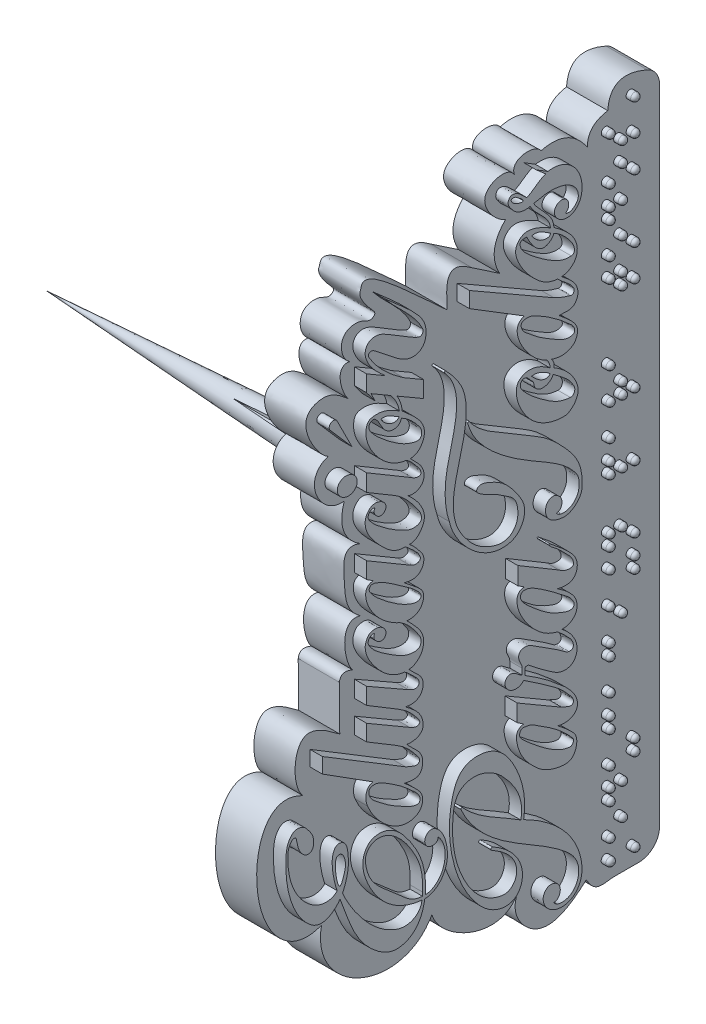
SolidWorks part; units mm, degrees
ref_plane "Alzado" through (0, 0, 0) normal (1, 0, 0) x (0, 1, 0)
ref_plane "Planta" through (0, 0, 0) normal (0, 0, 1) x (0, 1, 0)
ref_plane "Vista lateral" through (0, 0, 0) normal (0, 1, 0) x (-1, 0, 0)
sketch "Croquis1" plane through (0, 0, 0) normal (1, 0, 0) x (0, 1, 0)
  line L0 (-102.9215, 14.1156) -> (89.1062, 14.1156) construction
  line L1 (-85, 70) -> (85, 70) construction
  line L2 (-85, 70) -> (-85, -70) construction
  line L3 (-85, -70) -> (85, -70) construction
  line L4 (85, 70) -> (85, -70) construction
  line L5 (-85, 70) -> (85, -70) construction
  line L6 (-85, -70) -> (85, 70) construction
  line L7 (-124.4201, -60.3496) -> (113.099, -60.3496) construction
  line L8 (-82.6448, -39.616) -> (-82.6448, -50.4608)
  line L9 (-82.6448, -50.4608) -> (81.3909, -50.4608)
  spline S0 degree 3 poles (-57.3183, 31.5751) (-59.6603, 37.38) (-50.6709, 49.5862) (-25.7042, 47.5365) (-26.6427, 38.3656) (-27.8824, 36.0647) knots 0 0 0 0 0.354827 0.843229 0.974584 0.974584 0.974584 0.974584
  spline S1 degree 3 poles (-27.8824, 36.0647) (-26.8745, 37.0409) (-21.9922, 38.7753) (-11.8785, 36.5221) (-18.2243, 28.7209) (-19.3798, 27.1503) knots 0.077094 0.077094 0.077094 0.077094 0.266164 0.614207 1 1 1 1
  spline S2 degree 1 poles (-19.3798, 27.1503) (-8.4844, 27.2308) knots 0 0 1 1
  spline S3 degree 2 poles (-8.4844, 27.2308) (-6.1864, 26.9833) (-7.4593, 24.0317) knots 0 0 0 1 1 1
  spline S4 degree 3 poles (-7.4593, 24.0317) (-5.479, 25.9604) (4.6696, 27.8327) (2.9757, 22.117) knots 0 0 0 0 1 1 1 1
  spline S5 degree 3 poles (2.9757, 22.117) (5.5942, 25.8408) (10.9508, 25.8036) (19.9981, 26.6673) (18.1231, 22.117) knots 0 0 0 0 0.550537 1 1 1 1
  spline S6 degree 2 poles (18.1231, 22.117) (21.9702, 28.2845) (29.0551, 26.0729) knots 0 0 0 1 1 1
  spline S7 degree 3 poles (29.0551, 26.0729) (28.1951, 31.7606) (38.0923, 36.9327) (40.4039, 29.9176) knots 0 0 0 0 1 1 1 1
  spline S8 degree 3 poles (40.4039, 29.9176) (40.8758, 31.7815) (51.1967, 39.0102) (54.1428, 29.6378) (51.4152, 26.7401) (50.0352, 25.0248) knots 0 0 0 0 0.547016 0.715017 1 1 1 1
  spline S9 degree 3 poles (50.0352, 25.0248) (51.2452, 26.4664) (58.6684, 28.9911) (57.6422, 24.5742) knots 0 0 0 0 1 1 1 1
  spline S10 degree 3 poles (57.6422, 24.5742) (58.5649, 26.5416) (64.4147, 28.0831) (65.4745, 22.2237) (63.4708, 19.7827) (64.7939, 18.3202) (66.36, 19.8599) (69.5572, 22.3126) (71.0006, 22.3852) (71.715, 21.8879) (76.7031, 21.8392) (57.3827, 1.9867) (56.8213, 1.1788) knots 0 0 0 0 0.22866 0.372767 0.46177 0.486324 0.534034 0.642403 0.758615 0.782831 0.884561 1 1 1 1
  spline S11 degree 3 poles (-57.3183, 31.5751) (-71.6053, 34.513) (-81.578, 12.1878) (-68.5411, 4.7917) knots 0 0 0 0 1 1 1 1
  spline S12 degree 3 poles (-68.5411, 4.7917) (-75.1077, 2.9582) (-82.4626, -11.6999) (-74.4154, -15.9897) knots 0 0 0 0 1 1 1 1
  spline S13 degree 3 poles (-74.4154, -15.9897) (-78.3688, -14.0059) (-87.8936, -20.9461) (-83.6056, -28.6593) (-79.9178, -32.6901) knots 0 0 0 0 0.492525 1 1 1 1
  spline S14 degree 3 poles (-79.9178, -32.6901) (-84.1528, -34.8815) (-82.6448, -36.9407) (-82.6448, -39.616) knots 0 0 0 0 1 1 1 1
  spline S15 degree 3 poles (56.8213, 1.1788) (59.4241, 0.8853) (68.4666, 2.8376) (62.5364, -4.9778) knots 0 0 0 0 1 1 1 1
  spline S16 degree 1 poles (62.5364, -4.9778) (58.0243, -11.665) knots 0 0 1 1
  spline S17 degree 2 poles (58.0243, -11.665) (63.9267, -8.3863) (68.6781, -13.114) knots 0 0 0 1 1 1
  spline S18 degree 3 poles (68.6781, -13.114) (69.3817, -10.7651) (75.4734, -5.4705) (79.0736, -11.5853) (78.2326, -14.5514) (76.8919, -15.2804) knots 0 0 0 0 0.53381 0.759379 0.979689 0.979689 0.979689 0.979689
  spline S19 degree 3 poles (76.8919, -15.2804) (77.831, -14.9048) (80.7449, -15.427) (80.5824, -20.5896) (78.7651, -21.726) knots 0.033423 0.033423 0.033423 0.033423 0.278907 1 1 1 1
  spline S20 degree 2 poles (78.7651, -21.726) (80.5238, -28.3502) (73.9377, -32.9389) knots 0 0 0 1 1 1
  spline S21 degree 2 poles (73.9377, -32.9389) (78.3158, -32.9335) (79.1127, -37.8873) knots 0 0 0 1 1 1
  spline S22 degree 2 poles (79.1127, -37.8873) (88.058, -38.6156) (81.3909, -50.4608) knots 0 0 0 1 1 1
  point P0 (0, 0)
  dimension "D1" = 170
  dimension "D2" = 140
extrude "Saliente-Extruir2" add sketch "Croquis1" along normal blind 10
sketch "Croquis2" plane through (0, 0, 0) normal (-1, 0, 0) x (0, -1, 0)
  line L0 (0.6269, -50.4608) -> (0.6269, 25.9378) construction
  line L1 (82.6448, -50.4608) -> (-81.3909, -50.4608) construction
  line L2 (82.6448, -1.5809) -> (-84.2357, -1.5809) construction
  line L3 (82.6448, -50.4608) -> (-84.2357, -50.4608) construction
  line L4 (82.6448, -50.4608) -> (82.6448, 47.299) construction
  line L5 (82.6448, 47.299) -> (-84.2357, 47.299) construction
  line L6 (-84.2357, -50.4608) -> (-84.2357, 47.299) construction
  line L7 (82.6448, -11.5809) -> (-84.2357, -11.5809) construction
  parabola Q0 (-81.3909, -50.4608) -> (-79.1127, -37.8873) focus (-82.0968, -40.8467) apex (-83.5176, -39.835) construction
  parabola Q1 (-81.3909, -50.4608) -> (-79.1127, -37.8873) focus (-82.0968, -40.8467) apex (-83.5176, -39.835) construction
  spline S0 degree 3 poles (-2.9757, 22.117) (-4.6696, 27.8327) (5.479, 25.9604) (7.4593, 24.0317) knots 0 0 0 0 1 1 1 1 construction
  spline S1 degree 3 poles (27.8824, 36.0647) (26.6427, 38.3656) (25.7042, 47.5365) (50.6709, 49.5862) (59.6603, 37.38) (57.3183, 31.5751) knots 0 0 0 0 0.131354 0.619757 0.974584 0.974584 0.974584 0.974584 construction
  point P11 (40.0069, 47.299)
  point P17 (-84.2357, -42.2008)
  dimension "D1" = 8.26
  dimension "D2" = 39.38
  dimension "D3" = 10
ref_plane "Plano1" through (0, -0.6269, 0) normal (0, 1, 0) x (0, 0, 1)
sketch "Croquis3" plane through (0, -0.6269, 0) normal (0, 1, 0) x (0, 0, 1)
  line L0 (-11.665, 0) -> (-11.665, -100)
  line L1 (-11.665, -100) -> (-5.665, 0)
  line L2 (-50.4608, 0) -> (47.299, 0) construction
  line L3 (-5.665, 0) -> (-11.665, 0)
  dimension "D1" = 6
  dimension "D2" = 100
revolve "Revolución1" add sketch "Croquis3" angle 360 about L0
sketch "Croquis4" plane through (0, 0, 0) normal (-1, 0, 0) x (0, -1, 0)
  line L0 (0.6269, -17.665) -> (0.6269, -5.665) construction
  line L1 (-5.3731, -11.665) -> (6.6269, -11.665) construction
  line L2 (2.6269, -17.3219) -> (2.6269, -13.665)
  line L4 (2.6269, -6.0081) -> (2.6269, -9.665)
  line L5 (2.6269, -9.665) -> (6.2838, -9.665)
  line L7 (2.6269, -13.665) -> (6.2838, -13.665)
  line L8 (-1.3731, -17.3219) -> (-1.3731, -13.665)
  line L9 (-1.3731, -13.665) -> (-5.0299, -13.665)
  line L10 (-1.3731, -6.0081) -> (-1.3731, -9.665)
  line L11 (-1.3731, -9.665) -> (-5.0299, -9.665)
  circle A0 centre (0.6269, -11.665) radius 6 construction
  arc A1 (6.2838, -9.665) -> (2.6269, -6.0081) centre (0.6269, -11.665) ccw
  arc A2 (6.2838, -13.665) -> (2.6269, -17.3219) centre (0.6269, -11.665) cw
  arc A3 (-5.0299, -13.665) -> (-1.3731, -17.3219) centre (0.6269, -11.665) ccw
  arc A4 (-5.0299, -9.665) -> (-1.3731, -6.0081) centre (0.6269, -11.665) cw
  point P6 (0.6269, -11.665)
  point P8 (0.6269, -11.665)
  dimension "D1" = 4
  dimension "D2" = 4
extrude "Cortar-Extruir1" cut sketch "Croquis4" along normal through all
sketch "Croquis5" plane through (10, 0, 0) normal (1, 0, 0) x (0, 1, 0)
  line L0 (-30.4977, 22.0411) -> (-22.6878, 34.3782)
  line L1 (-22.6878, 34.3782) -> (-18.9988, 34.3782)
  line L2 (-18.9988, 34.3782) -> (-31.2431, 14.2065)
  line L3 (-25.6704, 16.365) -> (-21.3142, 23.6252)
  line L4 (-21.3142, 23.6252) -> (-17.3898, 23.6252)
  line L5 (-17.3898, 23.6252) -> (-23.4923, 13.1469)
  line L6 (-18.26, 15.9553) -> (-13.6411, 23.6252)
  line L7 (-13.6411, 23.6252) -> (-9.6181, 23.6252)
  line L8 (-9.6181, 23.6252) -> (-15.3979, 13.483)
  line L9 (11.7696, 22.0411) -> (12.8183, 23.6252)
  line L10 (12.8183, 23.6252) -> (16.7733, 23.6252)
  line L11 (16.7733, 23.6252) -> (10.6011, 13.1469)
  line L12 (27.0179, 16.7117) -> (31.1151, 23.6252)
  line L13 (31.1151, 23.6252) -> (35.2573, 23.6252)
  line L14 (35.2573, 23.6252) -> (28.6961, 12.5539)
  line L15 (49.3274, 21.5592) -> (52.0818, 23.6252)
  line L16 (52.0818, 23.6252) -> (56.0401, 23.6252)
  line L17 (56.0401, 23.6252) -> (53.3778, 19.0421)
  line L18 (49.3274, 21.5592) -> (51.3704, 22.5922)
  line L19 (51.3704, 22.5922) -> (48.5969, 17.8177)
  line L20 (47.708, 16.2875) -> (43.9264, 9.7775)
  line L21 (43.9264, 9.7775) -> (47.9268, 9.7775)
  line L22 (47.9268, 9.7775) -> (50.7842, 14.6965)
  line L23 (-36.5891, -14.4731) -> (-35.5305, -12.9048)
  line L24 (-35.5305, -12.9048) -> (-31.3942, -12.9048)
  line L25 (-31.3942, -12.9048) -> (-37.6673, -23.6868)
  line L26 (-7.8732, -14.6713) -> (-6.8254, -13.0472)
  line L27 (-6.8254, -13.0472) -> (-2.5643, -13.0472)
  line L28 (-2.5643, -13.0472) -> (-8.5231, -23.0594)
  line L29 (49.0645, -14.6713) -> (57.2905, -1.3112)
  line L30 (57.2905, -1.3112) -> (61.1001, -1.3112)
  line L31 (61.1001, -1.3112) -> (49.3274, -21.8088)
  line L32 (-60.5363, 10.0615) -> (-59.6392, 10.0615)
  line L33 (42.5241, 27.1794) -> (48.6046, 32.4718)
  line L34 (42.5241, 27.1794) -> (49.7281, 30.7967)
  line L35 (-26.5452, -14.7609) -> (-25.0608, -14.7609)
  line L36 (-26.1554, -14.1147) -> (-24.6961, -14.1147)
  line L37 (76.3432, -19.832) -> (78.3569, -17.5177)
  line L38 (78.3569, -17.5177) -> (76.6086, -20.3374)
  arc A0 (48.6046, 32.4718) -> (49.7281, 30.7967) centre (49.272, 31.7051) cw
  arc A1 (46.7383, 4.7071) -> (47.0407, 4.379) centre (46.8895, 4.5431) cw
  ellipse E0 centre (34.8468, 28.3326) end of major axis (36.1076, 30.4854) minor radius 2.1626
  spline S0 degree 3 poles (-32.8753, 40.7809) (-34.3802, 40.4669) (-37.0315, 40.1552) (-37.9946, 37.6514) (-37.3498, 36.6243) (-36.0991, 36.4283) (-34.4623, 36.5674) (-32.8648, 37.7082) (-31.5106, 38.7912) (-31.1895, 40.0213) (-31.1194, 41.2018) (-32.1231, 42.2284) (-33.817, 43.0691) (-35.9852, 43.257) (-42.6275, 43.2661) (-49.4687, 41.3481) (-53.3655, 36.734) (-54.6854, 33.7936) (-52.5646, 31.007) (-51.081, 30.0928) knots 0 0 0 0 0.108114 0.133301 0.15011 0.176379 0.206942 0.251601 0.297171 0.308781 0.330505 0.367881 0.388722 0.449419 0.4998 0.809316 0.834126 0.878153 1 1 1 1
  spline S1 degree 3 poles (-48.9999, 30.777) (-50.0879, 31.7419) (-50.4065, 34.7517) (-48.0166, 38.3827) (-44.5897, 40.971) (-40.6201, 42.4403) (-36.9284, 42.8214) (-33.9844, 42.7371) (-32.5521, 41.5219) (-32.8753, 40.7809) knots 0 0 0 0 0.159033 0.321236 0.4893 0.658852 0.811177 0.925085 1 1 1 1
  spline S2 degree 3 poles (-48.9999, 30.777) (-47.1529, 31.4095) (-44.3644, 32.0377) (-41.1112, 32.0057) (-39.4998, 31.2812) (-39.2053, 30.0434) (-39.8032, 28.827) (-41.2423, 28.2718) (-43.0409, 28.1097) (-44.7609, 27.9724) (-47.3, 28.3578) (-48.9998, 28.8703) (-50.1929, 29.4683) knots 0 0 0 0 0.260758 0.368098 0.436423 0.467936 0.526484 0.597505 0.66092 0.767128 0.823696 1 1 1 1
  spline S3 degree 3 poles (-46.1216, 28.9658) (-49.4615, 30.1919) (-46.2018, 31.0145) (-44.5749, 31.1947) (-43.0781, 31.2524) (-41.8296, 31.0322) (-41.5877, 30.1974) (-41.9671, 29.4227) (-42.8967, 29.028) (-44.5301, 28.6081) (-46.1216, 28.9658) (-49.4615, 30.1919) (-46.2018, 31.0145) knots -0.383453 -0.313119 -0.129387 0 0.154158 0.272418 0.382012 0.456693 0.492971 0.539173 0.616547 0.686881 0.870613 1 1.154158 1.272418 1.382012 only from (-48.3835, 30.0928) to (-48.3835, 30.0928)
  spline S4 degree 3 poles (-51.081, 30.0928) (-54.3854, 28.7515) (-60.3811, 27.0599) (-66.2373, 22.0009) (-69.1599, 16.8685) (-67.2807, 11.1802) (-63.3803, 9.8373) (-61.3313, 9.5286) knots 0 0 0 0 0.318574 0.533737 0.673711 0.810653 1 1 1 1
  spline S5 degree 3 poles (-50.1929, 29.4683) (-52.7679, 28.3332) (-57.9916, 25.0937) (-63.2745, 19.7033) (-65.3126, 13.4525) (-63.4453, 10.3811) (-61.253, 10.221) knots 0 0 0 0 0.305324 0.676273 0.795053 1 1 1 1
  spline S6 degree 3 poles (-61.253, 10.221) (-61.0094, 12.9445) (-59.1446, 17.8712) (-54.1089, 22.0097) (-49.5346, 24.1939) (-45.6585, 24.963) (-42.2603, 23.05) (-41.833, 19.6005) (-43.3284, 16.5185) (-45.8717, 14.1634) (-48.6344, 12.3059) (-53.2209, 9.7295) (-57.471, 9.1432) (-60.5363, 9.3474) knots 0 0 0 0 0.157619 0.290223 0.363353 0.451183 0.506001 0.566054 0.62999 0.698057 0.763117 0.821877 1 1 1 1
  spline S7 degree 3 poles (-60.5363, 10.0615) (-60.4315, 10.7862) (-60.1786, 12.5343) (-57.9714, 15.1639) (-55.0045, 18.4788) (-51.8323, 22.3612) (-47.8915, 23.8396) (-44.7064, 24.0894) (-42.809, 21.9292) (-43.024, 19.0148) (-45.4064, 15.3815) (-49.5738, 12.4184) (-54.7209, 10.0546) (-58.0346, 10.0592) (-59.6392, 10.0615) knots 0 0 0 0 0.045785 0.110435 0.210486 0.334029 0.417166 0.475731 0.520954 0.580199 0.646906 0.791941 0.899251 1 1 1 1
  spline S8 degree 3 poles (-49.9407, 6.2825) (-50.7221, 6.2114) (-51.3167, 7.3771) (-50.7667, 9.067) (-49.2157, 9.7669) (-47.8688, 9.1169) (-47.4082, 7.9224) (-47.8668, 6.803) (-48.9098, 5.6745) (-50.6697, 4.6821) (-53.2743, 4.0227) (-56.0005, 3.9217) (-58.2431, 4.789) (-60.3787, 6.3007) (-61.3542, 8.1142) (-61.3313, 9.5286) knots 0 0 0 0 0.071311 0.131011 0.190199 0.247337 0.285436 0.329154 0.380499 0.464884 0.561183 0.694994 0.776359 0.838641 1 1 1 1
  spline S9 degree 3 poles (-60.5363, 9.3474) (-60.564, 8.4483) (-59.8552, 6.8761) (-56.3738, 3.9845) (-51.9735, 4.3417) (-49.9407, 6.2825) knots 0 0 0 0 0.198499 0.371277 1 1 1 1
  spline S10 degree 2 poles (-41.6654, 18.06) (-38.9768, 21.6923) (-34.8857, 23.4339) knots 0 0 0 1 1 1
  spline S11 degree 3 poles (-34.8857, 23.4339) (-34.0906, 23.7515) (-32.3111, 24.0568) (-30.572, 23.1832) (-30.4977, 22.0411) knots 0 0 0 0 0.485788 1 1 1 1
  spline S12 degree 3 poles (-41.6654, 18.06) (-42.3986, 16.9398) (-43.3898, 15.0022) (-43.2455, 12.1543) (-41.8787, 10.0564) (-39.1625, 9.8582) (-36.8543, 11.8502) (-35.5255, 13.3917) (-34.6128, 14.4067) knots 0 0 0 0 0.236614 0.362101 0.48322 0.639456 0.763526 1 1 1 1
  spline S13 degree 3 poles (-40.6946, 10.9609) (-40.3903, 12.8252) (-39.1448, 14.9393) (-37.6665, 17.8519) (-35.4327, 20.6084) (-33.7314, 23.1321) (-31.7518, 23.1007) (-31.2827, 22.5692) (-31.0851, 21.3705) (-31.8864, 19.5488) (-33.392, 17.2339) (-35.0824, 14.7482) (-37.0941, 12.6053) (-38.4647, 10.9995) (-39.8145, 10.5247) (-40.6946, 10.9609) (-40.3903, 12.8252) (-39.1448, 14.9393) knots -0.083981 -0.054525 -0.041628 0 0.085966 0.20646 0.292539 0.428731 0.44798 0.464095 0.49008 0.557009 0.641477 0.750478 0.835345 0.916019 0.945475 0.958372 1 1.085966 1.20646 1.292539 only from (-40.4476, 12.1724) to (-40.4476, 12.1724)
  spline S14 degree 3 poles (-31.2431, 14.2065) (-31.4954, 13.791) (-31.7805, 12.8244) (-32.3805, 11.7184) (-31.94, 10.716) (-31.0117, 10.8255) (-30.1202, 11.5734) (-28.0239, 13.1991) (-26.5761, 14.8553) (-25.6704, 16.365) knots 0 0 0 0 0.125392 0.242085 0.298963 0.348525 0.442223 0.588193 1 1 1 1
  spline S15 degree 3 poles (-34.6128, 14.4067) (-34.7496, 13.4983) (-35.4629, 10.853) (-32.8319, 9.9131) (-29.6395, 10.1767) (-28.0685, 12.8244) (-26.67, 13.9022) knots 0 0 0 0 0.278768 0.418048 0.563003 1 1 1 1
  spline S16 degree 3 poles (-26.67, 13.9022) (-26.9516, 12.9077) (-26.6145, 9.794) (-21.7377, 9.9597) (-19.9279, 12.5545) (-18.6511, 14.2065) knots 0 0 0 0 0.313936 0.487109 1 1 1 1
  spline S17 degree 3 poles (-23.4923, 13.1469) (-23.7092, 12.5749) (-24.4199, 11.749) (-23.7114, 10.5495) (-22.7044, 11.0703) (-20.8333, 12.6799) (-19.6018, 13.7273) (-18.26, 15.9553) knots 0 0 0 0 0.194853 0.255549 0.328019 0.466069 1 1 1 1
  spline S18 degree 3 poles (-18.6511, 14.2065) (-18.8985, 13.209) (-18.944, 11.198) (-16.9063, 9.8461) (-13.827, 9.881) (-12.4616, 12.4027) (-11.1951, 13.3111) knots 0 0 0 0 0.281686 0.412944 0.576334 1 1 1 1
  spline S19 degree 3 poles (-15.3979, 13.483) (-15.6328, 12.976) (-16.4144, 11.8498) (-15.4388, 10.7448) (-14.194, 11.1159) (-12.9561, 12.5512) (-11.7383, 13.604) (-11.1951, 14.496) knots 0 0 0 0 0.252349 0.329617 0.447788 0.639049 1 1 1 1
  spline S20 degree 3 poles (-11.1951, 13.3111) (-11.1786, 12.6141) (-10.61, 11.4044) (-9.2667, 10.2) (-7.7421, 9.764) (-4.407, 9.7889) (-2.2388, 12.4696) (-0.6949, 13.9022) knots 0 0 0 0 0.148996 0.285512 0.38061 0.491113 1 1 1 1
  spline S21 degree 3 poles (-11.1951, 14.496) (-11.1257, 15.8129) (-9.8111, 18.7994) (-6.291, 21.994) (-2.9718, 23.9384) (-0.7617, 23.9955) (0.1528, 23.6663) (1.0645, 23.1384) (1.4373, 22.0629) (1.4623, 20.8899) (0.8662, 19.7313) (0.0333, 19.0277) (-0.8625, 18.8995) (-1.7284, 19.195) (-1.9636, 20.256) (-1.2566, 21.5002) (-0.2394, 22.2156) (0.5693, 21.6497) knots 0 0 0 0 0.142885 0.345562 0.51692 0.54408 0.584366 0.622837 0.653405 0.704139 0.747462 0.792556 0.816848 0.844533 0.884115 0.91523 1 1 1 1
  spline S22 degree 3 poles (0.5693, 21.6497) (0.7039, 22.1733) (0.3651, 23.0472) (-0.8733, 23.4017) (-1.8324, 22.7341) (-3.1649, 21.6574) (-4.5178, 19.8541) (-6.1477, 17.3884) (-7.6569, 14.9172) (-8.2509, 12.6201) (-8.0802, 10.6437) (-6.2269, 10.2196) (-3.5165, 12.0259) (-1.4681, 13.63) (-0.3081, 15.5121) knots 0 0 0 0 0.059858 0.084589 0.133112 0.178045 0.278694 0.378635 0.509425 0.593264 0.648482 0.700592 0.76797 1 1 1 1
  spline S23 degree 3 poles (-0.3081, 15.5121) (0.4824, 17.2717) (2.304, 20.0154) (5.6832, 22.6917) (8.9806, 24.0787) (11.5742, 23.9247) (11.7696, 22.0411) knots 0 0 0 0 0.349521 0.588759 0.767778 1 1 1 1
  spline S24 degree 3 poles (-0.6949, 13.9022) (-0.9343, 12.7942) (-0.4522, 10.7658) (1.6189, 9.7936) (2.8478, 9.75) (3.8626, 10.1492) (5.493, 11.6662) (6.5376, 13.3498) (7.5617, 14.496) knots 0 0 0 0 0.267509 0.402149 0.498611 0.541617 0.649789 1 1 1 1
  spline S25 degree 3 poles (7.6462, 15.9241) (10.1866, 19.0064) (11.1853, 21.9828) (11.0882, 22.7824) (10.2945, 23.1392) (9.5666, 22.7365) (8.208, 21.7006) (6.1295, 19.2883) (3.7662, 16.0444) (2.2798, 13.072) (1.9119, 11.1988) (2.4385, 10.3789) (3.296, 10.4425) (3.9842, 11.0502) (4.5955, 11.7225) (5.5919, 12.7416) (7.6462, 15.9241) (10.1866, 19.0064) (11.1853, 21.9828) knots -0.355516 -0.339725 -0.248943 0 0.025214 0.046912 0.068041 0.09466 0.119729 0.23059 0.389513 0.497031 0.541805 0.563228 0.573881 0.617524 0.644484 0.660275 0.751057 1 1.025214 1.046912 1.068041 only from (10.9335, 21.2609) to (10.9335, 21.2609)
  spline S26 degree 3 poles (10.6011, 13.1469) (10.4033, 12.8112) (9.8549, 11.8359) (10.4667, 10.2937) (11.9078, 10.9475) (13.2454, 12.1923) (14.3707, 13.3792) (15.0135, 14.2065) knots 0 0 0 0 0.18999 0.314253 0.460996 0.61937 1 1 1 1
  spline S27 degree 3 poles (7.5617, 14.496) (7.2677, 13.4828) (6.9121, 11.0987) (9.183, 9.7347) (11.0782, 9.6872) (12.9527, 11.231) (14.3116, 12.3091) (15.0135, 13.3111) knots 0 0 0 0 0.288267 0.445397 0.571944 0.717436 1 1 1 1
  spline S28 degree 3 poles (15.0135, 14.2065) (14.8615, 16.7526) (17.5133, 19.6933) (21.0407, 22.7822) (23.9338, 24.1476) (26.4814, 23.8973) (27.9531, 22.308) (27.723, 20.3882) (26.7443, 18.9146) (24.8751, 18.8823) (24.3226, 20.3976) (25.2344, 21.6158) (26.2623, 22.0942) (26.8814, 21.5592) knots 0 0 0 0 0.257469 0.404494 0.516094 0.593904 0.669355 0.720454 0.795978 0.839171 0.895119 0.925934 1 1 1 1
  spline S29 degree 3 poles (26.8814, 21.5592) (27.0954, 22.0247) (26.9036, 22.9292) (25.5957, 23.4629) (24.3413, 22.5871) (23.1722, 21.4419) (21.0572, 18.7443) (18.9909, 15.6579) (17.652, 12.21) (18.505, 10.1974) (20.0998, 10.3899) (21.243, 11.1001) (23.8006, 13.0162) (25.9385, 14.8902) (27.0179, 16.7117) knots 0 0 0 0 0.049092 0.083265 0.127241 0.194236 0.257104 0.479655 0.581589 0.628504 0.6687 0.72549 0.770635 1 1 1 1
  spline S30 degree 3 poles (15.0135, 13.3111) (14.9143, 11.9258) (16.3437, 10.3322) (18.913, 9.3832) (22.2509, 10.3688) (24.2046, 12.2466) (25.5195, 13.7107) knots 0 0 0 0 0.276983 0.422942 0.572023 1 1 1 1
  spline S31 degree 3 poles (25.5195, 13.7107) (24.8284, 12.5371) (25.5252, 9.7865) (29.9097, 9.4817) (31.6722, 11.8848) (32.9555, 13.0649) knots 0 0 0 0 0.341874 0.528238 1 1 1 1
  spline S32 degree 3 poles (28.6961, 12.5539) (28.421, 12.3856) (27.6888, 10.3026) (29.5345, 10.5614) (30.9642, 11.8817) (32.4321, 12.9727) (33.0696, 14.0259) knots 0 0 0 0 0.260801 0.352343 0.552857 1 1 1 1
  spline S33 degree 3 poles (33.0696, 14.0259) (33.4098, 16.9926) (36.39, 20.8729) (41.2096, 23.598) (44.1316, 23.9082) (46.0104, 23.4117) (46.7526, 19.96) (45.5118, 17.6923) (44.3075, 15.6952) knots 0 0 0 0 0.340662 0.54387 0.625452 0.689244 0.744404 1 1 1 1
  spline S34 degree 3 poles (32.9555, 13.0649) (32.854, 10.9485) (38.4119, 7.3412) (42.3173, 13.4151) (43.9264, 15.0017) knots 0 0 0 0 0.387765 1 1 1 1
  spline S35 degree 3 poles (43.0647, 15.6952) (43.7052, 17.0431) (45.1478, 18.4945) (44.8019, 20.1684) knots 0 0 0 0 1 1 1 1
  spline S36 degree 3 poles (44.8019, 20.1684) (44.0548, 19.8014) (42.7981, 18.519) (42.1784, 16.5118) (43.0647, 15.6952) knots 0 0 0 0 0.44386 1 1 1 1
  spline S37 degree 3 poles (42.5241, 15.1835) (41.1069, 15.4879) (40.6761, 17.8412) (42.904, 20.1193) (44.7136, 20.6463) (45.5384, 21.6497) knots 0 0 0 0 0.390264 0.598106 1 1 1 1
  spline S38 degree 3 poles (45.5384, 21.6497) (45.6879, 22.0521) (45.5094, 22.8336) (44.2166, 23.2814) (42.868, 22.3291) (40.5799, 20.1613) (38.0542, 16.8143) (36.2183, 13.6653) (35.4577, 10.2113) (37.7346, 10.2131) (39.964, 11.8499) (41.6353, 13.5109) (42.5241, 15.1835) knots 0 0 0 0 0.048159 0.074575 0.142627 0.215099 0.445179 0.592365 0.67817 0.744905 0.783216 1 1 1 1
  spline S39 degree 2 poles (44.3075, 15.6952) (46.7398, 16.1406) (48.5969, 17.8177) knots 0 0 0 1 1 1
  spline S40 degree 2 poles (43.9264, 15.0017) (45.98, 15.1594) (47.708, 16.2875) knots 0 0 0 1 1 1
  spline S41 degree 3 poles (50.7842, 14.6965) (52.0833, 16.6653) (54.755, 19.8637) (57.5835, 22.0099) (59.8678, 23.6226) (60.3434, 22.546) (59.9837, 21.6571) (58.8911, 20.4106) (56.8866, 17.6325) (54.3379, 15.0319) (53.8506, 11.7982) (55.041, 9.2902) (59.2609, 8.8256) (64.3855, 12.7442) (67.2658, 16.7314) (69.6392, 19.2427) knots 0 0 0 0 0.165295 0.229847 0.273783 0.283531 0.295769 0.332829 0.390387 0.517595 0.555804 0.593627 0.683261 0.77817 1 1 1 1
  spline S42 degree 3 poles (53.3778, 19.0421) (54.9172, 20.837) (57.0974, 23.2466) (60.8494, 24.2322) (62.813, 23.152) (63.0595, 20.7089) (61.6462, 18.2333) (59.9447, 15.4682) (58.4586, 13.0439) (57.6148, 11.4751) (57.2016, 10.1519) (58.3799, 9.7673) (58.7573, 10.0615) knots 0 0 0 0 0.271835 0.349442 0.418952 0.493831 0.597399 0.735632 0.864555 0.912432 0.945486 1 1 1 1
  spline S43 degree 3 poles (58.7573, 10.0615) (63.1297, 12.1263) (65.89, 16.3496) (69.6392, 19.2427) knots 0 0 0 0 1 1 1 1
  spline S44 degree 3 poles (-77.7132, -21.8088) (-77.8735, -22.5885) (-76.4065, -23.7156) (-73.9921, -22.9996) (-73.2849, -20.5623) (-74.9074, -19.1117) (-77.0095, -19.2288) (-78.9593, -20.7202) (-79.9036, -23.3069) (-79.3953, -26.3135) (-76.4288, -28.8177) (-66.0802, -28.4453) (-59.7243, -20.627) (-56.7, -14.4731) knots 0 0 0 0 0.04565 0.092837 0.139769 0.175601 0.2131 0.265378 0.322636 0.380629 0.44868 0.549274 1 1 1 1
  spline S45 degree 3 poles (-77.7132, -21.8088) (-78.526, -22.1526) (-78.9151, -23.8635) (-78.1263, -26.5557) (-75.1385, -28.1492) (-71.0923, -27.5269) (-67.1718, -23.363) (-63.2221, -16.9617) (-57.746, -7.3421) (-51.6634, -1.3146) (-46.9788, 0.74) knots 0 0 0 0 0.049068 0.093814 0.163881 0.231302 0.329294 0.495952 0.692771 1 1 1 1
  spline S46 degree 2 poles (-46.9788, 0.74) (-46.5446, 0.8724) (-46.6703, 0.3952) knots 0 0 0 1 1 1
  spline S47 degree 3 poles (-56.4038, -13.7656) (-55.2229, -11.9723) (-52.4754, -6.9285) (-49.4695, -1.9971) (-46.6703, 0.3952) knots 0 0 0 0 0.372986 1 1 1 1
  spline S48 degree 3 poles (-56.4038, -13.7656) (-51.946, -14.8339) (-47.7753, -12.0465) (-44.8075, -9.1089) knots 0 0 0 0 1 1 1 1
  spline S49 degree 3 poles (-44.8075, -9.1089) (-42.9051, -7.1355) (-40.7396, -3.2113) (-42.6971, 1.1604) (-45.155, 2.4565) (-48.2121, 2.7877) (-54.6295, 2.8536) (-61.8555, 0.7868) (-67.7823, -3.8603) (-69.8464, -7.5294) (-70.2912, -10.9075) (-67.9798, -12.9787) (-64.7621, -12.7783) (-62.2764, -10.9565) (-60.5501, -8.8792) (-59.7063, -7.5179) (-59.3371, -6.8677) knots 0 0 0 0 0.145644 0.19204 0.226794 0.282059 0.347508 0.554579 0.649341 0.723343 0.767565 0.808865 0.862512 0.918538 0.961832 1 1 1 1
  spline S50 degree 3 poles (-59.3371, -6.8677) (-59.289, -6.783) (-59.1483, -6.4496) (-58.4956, -6.5783) (-58.7145, -7.0018) knots 0 0 0 0 0.254939 1 1 1 1
  spline S51 degree 3 poles (-58.7145, -7.0018) (-59.437, -8.3283) (-60.6271, -10.052) (-63.2185, -12.5967) (-66.1095, -14.2509) (-69.7291, -14.2645) (-72.0631, -12.8687) (-72.868, -10.7537) (-72.4125, -6.4313) (-67.3247, -1.5104) (-59.9704, 2.0403) (-52.2986, 3.696) (-45.2198, 3.5092) (-37.1597, 1.1984) (-37.5757, -5.8987) (-40.5563, -10.0823) (-46.5642, -13.8736) (-52.5753, -15.204) (-56.7, -14.4731) knots 0 0 0 0 0.051997 0.071013 0.124963 0.161141 0.190974 0.211701 0.23536 0.336466 0.431244 0.519457 0.599455 0.683146 0.763363 0.792583 0.860139 1 1 1 1
  spline S52 degree 3 poles (-46.6703, -16.9161) (-44.7321, -14.8964) (-41.6235, -12.7294) (-36.876, -12.5225) (-36.5891, -14.4731) knots 0 0 0 0 0.651484 1 1 1 1
  spline S53 degree 3 poles (-46.6703, -16.9161) (-48.5191, -18.6913) (-49.9145, -21.4014) (-50.2829, -26.0387) (-47.7738, -27.4709) (-45.2505, -27.456) (-43.155, -25.2065) (-41.8283, -23.8053) (-41.0276, -22.6758) knots 0 0 0 0 0.336873 0.480563 0.576285 0.713908 0.806228 1 1 1 1
  spline S54 degree 3 poles (-47.0965, -26.1737) (-46.9056, -24.4491) (-45.6648, -21.4152) (-42.8947, -17.8761) (-40.5416, -14.9868) (-38.6663, -13.143) (-37.1714, -13.9276) (-37.4295, -15.1379) (-37.5911, -16.4224) (-38.9236, -18.158) (-40.3032, -20.5945) (-42.502, -23.4794) (-44.3451, -25.387) (-46.0072, -26.8269) (-47.0965, -26.1737) (-46.9056, -24.4491) (-45.6648, -21.4152) knots -0.086597 -0.054034 -0.024168 0 0.09053 0.274154 0.38708 0.44562 0.476897 0.505932 0.544194 0.594983 0.694927 0.798763 0.913403 0.945966 0.975832 1 1.09053 1.274154 1.38708 only from (-46.9788, -25.2497) to (-46.9788, -25.2497)
  spline S55 degree 3 poles (-41.0276, -22.6758) (-41.6255, -23.91) (-41.2209, -27.5213) (-36.6993, -27.8149) (-33.4894, -24.2892) (-32.7831, -23.3094) knots 0 0 0 0 0.339105 0.559776 1 1 1 1
  spline S56 degree 3 poles (-37.6673, -23.6868) (-37.5412, -23.8836) (-39.2124, -26.1531) (-37.7255, -26.6568) (-36.7545, -26.2512) (-35.2676, -24.9225) (-33.1909, -22.9064) (-30.5442, -18.9981) (-28.9646, -16.9283) (-27.4283, -14.4731) knots 0 0 0 0 0.145252 0.175575 0.204105 0.303646 0.478716 0.653344 1 1 1 1
  spline S57 degree 3 poles (-32.7831, -23.3094) (-30.3896, -20.7067) (-28.3828, -17.7731) (-26.5452, -14.7609) knots 0 0 0 0 1 1 1 1
  spline S58 degree 3 poles (-27.4283, -14.4731) (-27.9497, -14.0765) (-28.4625, -12.9557) (-28.0552, -11.1559) (-26.871, -10.0151) (-25.3522, -9.8218) (-24.4025, -10.7433) (-24.5579, -11.8938) (-25.2849, -12.9196) (-25.8691, -13.6127) (-26.1554, -14.1147) knots 0 0 0 0 0.16828 0.299868 0.462898 0.570081 0.67008 0.761042 0.848906 1 1 1 1
  spline S59 degree 3 poles (-25.0608, -14.7609) (-24.671, -14.7609) (-24.7188, -15.6441) (-24.8153, -15.6725) knots 0 0 0 0 1 1 1 1
  spline S60 degree 3 poles (-24.8153, -15.6725) (-26.0602, -17.09) (-27.8729, -19.8233) (-30.6689, -23.3313) (-29.9796, -26.4574) (-26.1523, -28.6079) (-22.5405, -25.4894) (-21.3142, -23.6868) knots 0 0 0 0 0.247621 0.466642 0.549743 0.643826 1 1 1 1
  spline S61 degree 3 poles (-24.6961, -14.1147) (-23.782, -14.1102) (-22.8602, -13.1239) (-20.8227, -13.3147) (-20.3207, -15.196) (-21.4812, -17.1313) (-23.5192, -20.0906) (-25.1866, -23.0498) (-27.0056, -25.2164) (-26.6822, -26.6991) (-24.8461, -26.3934) (-23.3147, -24.8556) (-21.9691, -23.5126) (-21.3142, -22.6758) knots 0 0 0 0 0.100494 0.148462 0.20939 0.289546 0.409533 0.63759 0.695543 0.734759 0.779004 0.873028 1 1 1 1
  spline S62 degree 3 poles (-21.3142, -22.6758) (-20.6627, -19.7472) (-17.729, -16.3521) (-13.3828, -13.6451) (-10.2042, -12.636) (-7.9219, -12.9107) (-7.8732, -14.6713) knots 0 0 0 0 0.462898 0.689316 0.80455 1 1 1 1
  spline S63 degree 3 poles (-21.3142, -23.6868) (-21.457, -24.9085) (-20.4166, -27.4442) (-17.1117, -27.5665) (-14.4565, -25.7596) (-13.1896, -24.0493) (-12.2832, -22.6758) knots 0 0 0 0 0.287522 0.49879 0.650604 1 1 1 1
  spline S64 degree 3 poles (-18.4443, -25.5806) (-17.7518, -23.553) (-16.4912, -20.706) (-14.2286, -17.8259) (-12.1707, -15.4214) (-10.5865, -13.8817) (-9.2336, -13.5863) (-8.6209, -14.1177) (-8.5056, -15.2027) (-9.1874, -17.0207) (-10.6445, -19.1052) (-12.3208, -21.5452) (-14.282, -24.0034) (-15.8041, -26.1492) (-17.5294, -26.8251) (-18.1185, -26.5367) (-18.4443, -25.5806) (-17.7518, -23.553) (-16.4912, -20.706) knots -0.085408 -0.071009 -0.056836 0 0.110904 0.224901 0.322752 0.396741 0.416178 0.439156 0.458588 0.510414 0.607683 0.686285 0.774218 0.890306 0.914592 0.928991 0.943164 1 1.110904 1.224901 1.322752 only from (-17.9448, -24.1757) to (-17.9448, -24.1757)
  spline S65 degree 3 poles (-12.2832, -22.6758) (-12.5274, -23.7219) (-13.008, -26.3894) (-10.0978, -27.7479) (-7.5405, -27.1163) (-5.4439, -25.0714) (-3.5845, -22.9735) (-2.4587, -21.5553) (-2.0168, -20.9772) knots 0 0 0 0 0.227562 0.360002 0.497208 0.676097 0.870838 1 1 1 1
  spline S66 degree 3 poles (-8.5231, -23.0594) (-9.1138, -23.9079) (-9.7648, -25.0796) (-9.2835, -26.6187) (-8.3592, -26.5506) (-7.6742, -26.2524) (-6.7114, -25.6069) (-5.8294, -24.5506) (-4.4752, -23.3679) (-3.4317, -22.1563) (-2.7278, -21.0991) (-2.2376, -20.8019) knots 0 0 0 0 0.244457 0.274609 0.337332 0.412324 0.497476 0.582173 0.736319 0.868934 1 1 1 1
  spline S67 degree 3 poles (-2.2376, -20.8019) (-2.1577, -20.7533) (-2.05, -20.7097) (-1.9405, -20.8775) (-2.0168, -20.9772) knots 0 0 0 0 0.44797 1 1 1 1
  spline S68 degree 3 poles (3.7431, -22.3927) (3.6925, -23.0701) (4.5686, -23.8115) (6.1242, -23.8225) (7.0923, -23.0326) (7.7563, -22.0483) (7.7119, -20.8254) (6.3226, -19.4963) (3.834, -19.8746) (2.5125, -21.6811) (2.1264, -23.1995) (1.7966, -25.899) (4.1468, -28.6261) (6.6916, -28.6784) (8.3762, -28.6462) (12.1537, -28.1368) (16.3556, -24.7083) (21.0362, -20.0041) (23.9302, -14.7022) (27.9568, -8.1237) (30.5523, -3.3307) (33.5861, -1.3112) knots 0 0 0 0 0.028675 0.048966 0.070805 0.086305 0.105693 0.124295 0.173416 0.203628 0.229181 0.248876 0.335296 0.35537 0.372014 0.41735 0.537475 0.623118 0.740982 0.827448 1 1 1 1
  spline S69 degree 3 poles (3.7431, -22.3927) (2.9358, -22.99) (2.7825, -24.5951) (3.6622, -26.584) (5.225, -27.839) (7.1732, -27.9636) (8.9514, -27.8126) (10.6579, -26.5456) (12.3851, -24.8634) (14.8896, -21.4958) (18.2384, -15.3443) (23.6274, -7.0968) (29.6577, -1.9209) (33.3267, -0.9219) knots 0 0 0 0 0.060744 0.088394 0.138975 0.178207 0.211335 0.250688 0.310032 0.366531 0.518154 0.757636 1 1 1 1
  spline S70 degree 3 poles (33.3267, -0.9219) (33.4124, -0.8769) (33.745, -0.9353) (33.6128, -1.2413) (33.5861, -1.3112) knots 0 0 0 0 0.508376 1 1 1 1
  spline S71 degree 3 poles (8.8073, -0.9219) (9.9223, 0.0215) (12.1199, 1.5384) (15.9044, 2.6325) (20.2749, 2.625) (25.3394, 1.4552) (30.4111, 0.0347) (35.4542, -0.6993) (41.4474, -0.3303) (44.903, 2.4085) (47.0407, 4.379) knots 0 0 0 0 0.107829 0.194083 0.285762 0.426557 0.575595 0.672929 0.803041 1 1 1 1
  spline S72 degree 3 poles (8.8073, -0.9219) (7.8612, -1.6486) (6.4051, -3.1477) (5.0328, -5.6103) (4.1259, -8.0274) (3.9946, -10.929) (6.3859, -13) (9.1604, -13.1859) (12.0168, -12.5055) (13.4224, -10.174) (14.8411, -8.1781) (15.8862, -5.9007) (16.7895, -4.1993) (17.8977, -2.8826) (18.7921, -3.3107) (19.036, -4.4874) (18.307, -6.282) (16.7141, -9.7539) (13.1725, -12.646) (9.0386, -15.1264) (5.4891, -14.3727) (3.535, -12.4621) (1.4029, -4.6585) (9.673, 2.475) (14.9281, 3.542) knots 0 0 0 0 0.047894 0.08297 0.112114 0.152405 0.189684 0.225088 0.26218 0.3001 0.328739 0.361799 0.398509 0.411455 0.421491 0.4305 0.457011 0.496878 0.583612 0.635943 0.683369 0.716907 0.740553 1 1 1 1
  spline S73 degree 3 poles (14.9281, 3.542) (18.0051, 4.6061) (24.0118, 4.9627) (31.4645, 2.7602) (39.0257, 1.3215) (44.057, 2.2353) (46.7383, 4.7071) knots 0 0 0 0 0.29874 0.535955 0.713808 1 1 1 1
  spline S74 degree 3 poles (23.1694, -24.7793) (23.0336, -22.2804) (24.422, -17.3992) (29.4219, -13.7631) (33.2308, -12.6021) (35.8462, -12.7148) (38.0581, -16.0952) (36.25, -19.3081) (35.0454, -20.8827) knots 0 0 0 0 0.264379 0.508659 0.615545 0.692032 0.7635 1 1 1 1
  spline S75 degree 3 poles (23.1694, -24.7793) (23.6322, -26.2982) (25.9397, -28.2061) (30.8893, -26.7143) (33.277, -24.0968) (34.6179, -21.8088) knots 0 0 0 0 0.327278 0.464118 1 1 1 1
  spline S76 degree 3 poles (26.4086, -25.7574) (26.4671, -23.2169) (28.5861, -19.9951) (31.3079, -16.4066) (33.0844, -14.6432) (34.2902, -13.6689) (35.2713, -13.6394) (35.9739, -14.0757) (36.0295, -14.874) (35.6008, -15.5612) (34.8057, -16.0646) (34.3255, -16.6958) (33.9647, -16.9161) knots 0 0 0 0 0.36957 0.559837 0.675142 0.750597 0.780141 0.817699 0.862554 0.881992 0.937764 1 1 1 1
  spline S77 degree 3 poles (33.8327, -20.8827) (34.4202, -20.2287) (35.2866, -18.81) (35.69, -17.1687) (35.5179, -16.3843) knots 0 0 0 0 0.529809 1 1 1 1
  spline S78 degree 3 poles (33.8327, -20.8827) (33.4667, -20.7592) (32.8703, -18.8739) (34.6577, -17.2482) (35.5179, -16.3843) knots 0 0 0 0 0.18795 1 1 1 1
  spline S79 degree 3 poles (26.4086, -25.7574) (26.2702, -26.5211) (27.6563, -27.2473) (29.0426, -26.2812) (31.1759, -24.7981) (32.2648, -22.8757) (33.3267, -21.6332) knots 0 0 0 0 0.193156 0.359155 0.487732 1 1 1 1
  spline S80 degree 3 poles (33.3267, -21.6332) (31.2233, -20.8953) (30.9818, -16.9413) (33.9647, -16.9161) knots 0 0 0 0 1 1 1 1
  spline S81 degree 2 poles (35.0454, -20.8827) (36.2193, -20.88) (37.1434, -20.0597) knots 0 0 0 1 1 1
  spline S82 degree 2 poles (34.6179, -21.8088) (35.8303, -22.0246) (36.7129, -21.2213) knots 0 0 0 1 1 1
  spline S83 degree 3 poles (37.1434, -20.0597) (38.0321, -17.943) (40.6497, -15.4068) (45.0116, -12.8892) (48.4953, -12.4999) (49.0645, -14.6713) knots 0 0 0 0 0.438048 0.676243 1 1 1 1
  spline S84 degree 3 poles (36.7129, -21.2213) (36.2229, -22.4062) (35.9663, -24.3626) (37.0366, -26.6886) (38.5632, -27.5762) (40.3627, -27.593) (42.6624, -26.0099) (43.9342, -24.2495) (44.9775, -23.0594) knots 0 0 0 0 0.251229 0.359927 0.479127 0.572937 0.694875 1 1 1 1
  spline S85 degree 3 poles (39.4737, -26.9826) (38.9432, -25.5234) (39.5199, -23.5285) (40.9487, -21.3353) (42.4712, -18.5187) (44.4451, -16.1751) (46.0199, -14.1551) (48.0389, -13.6039) (48.5841, -15.7893) (47.6825, -17.5695) (45.6059, -21.1887) (43.2205, -24.3052) (40.8516, -26.7578) (39.4737, -26.9826) (38.9432, -25.5234) (39.5199, -23.5285) knots -0.098014 -0.050077 -0.016868 0 0.077907 0.163792 0.239766 0.369498 0.439477 0.47918 0.52175 0.600376 0.663491 0.901986 0.949923 0.983132 1 1.077907 1.163792 1.239766 only from (39.2182, -26.2204) to (39.2182, -26.2204)
  spline S86 degree 2 poles (49.3274, -21.8088) (48.3391, -23.7007) (47.8117, -25.7574) knots 0 0 0 1 1 1
  spline S87 degree 3 poles (47.8117, -25.7574) (47.4677, -26.4489) (48.4081, -26.9533) (50.5778, -25.7115) (51.5733, -23.8552) (52.833, -22.6758) knots 0 0 0 0 0.217033 0.277261 1 1 1 1
  spline S88 degree 3 poles (44.9775, -23.0594) (44.9586, -24.0872) (44.4412, -26.4062) (46.8802, -27.8153) (50.1201, -27.3621) (51.7228, -24.9844) (52.833, -23.6868) knots 0 0 0 0 0.271886 0.42664 0.570583 1 1 1 1
  spline S89 degree 3 poles (52.833, -22.6758) (52.9253, -20.1119) (55.8618, -16.5557) (60.1524, -13.3932) (64.4291, -11.9315) (66.519, -14.1895) (66.5474, -17.3751) (65.2404, -19.3942) (64.4428, -20.9772) knots 0 0 0 0 0.28484 0.494619 0.639608 0.741194 0.79047 1 1 1 1
  spline S90 degree 3 poles (52.833, -23.6868) (52.845, -25.1631) (54.3641, -27.4586) (59.8615, -27.6521) (62.5787, -23.8977) (64.0949, -21.8088) knots 0 0 0 0 0.28802 0.431178 1 1 1 1
  spline S91 degree 3 poles (56.0401, -26.0057) (55.8546, -24.2653) (57.2052, -21.4357) (59.6246, -17.944) (61.7593, -15.2678) (63.4844, -13.7451) (65.4237, -13.4399) (65.4013, -14.9021) (65.3324, -15.2409) knots 0 0 0 0 0.285454 0.511818 0.72396 0.856919 0.908472 1 1 1 1
  spline S92 degree 3 poles (56.0401, -26.0057) (56.0786, -26.8968) (57.8028, -26.8531) (60.3261, -25.1464) (62.0971, -23.3096) (62.8595, -21.8088) knots 0 0 0 0 0.199781 0.458676 1 1 1 1
  spline S93 degree 3 poles (63.3328, -20.9772) (64.215, -19.62) (65.452, -18.1368) (65.0094, -16.3843) knots 0 0 0 0 1 1 1 1
  spline S94 degree 3 poles (63.3328, -20.9772) (62.7588, -21.0196) (62.4079, -18.7529) (63.7195, -17.3591) (65.0094, -16.3843) knots 0 0 0 0 0.221175 1 1 1 1
  spline S95 degree 3 poles (62.8595, -21.8088) (61.8768, -21.4782) (59.5121, -18.1745) (64.324, -15.7206) (65.3324, -15.2409) knots 0 0 0 0 0.348085 1 1 1 1
  spline S96 degree 3 poles (64.0949, -21.8088) (67.3036, -21.7328) (69.0736, -18.304) (71.5914, -16.9161) knots 0 0 0 0 1 1 1 1
  spline S97 degree 3 poles (64.4428, -20.9772) (67.445, -20.6793) (68.8325, -17.2192) (71.4042, -16.0854) knots 0 0 0 0 1 1 1 1
  spline S98 degree 3 poles (71.4042, -16.0854) (71.1336, -14.9957) (71.3689, -12.9034) (73.2023, -11.4275) (74.615, -10.4225) (76.0523, -11.1193) (75.9492, -13.3196) (74.3877, -14.2884) (73.6628, -15.2409) knots 0 0 0 0 0.266848 0.419626 0.539161 0.639185 0.706232 1 1 1 1
  spline S99 degree 3 poles (74.0571, -14.0342) (73.114, -14.5265) (73.4447, -13.1082) (73.813, -12.3355) (74.3731, -11.6161) (75.102, -11.3733) (75.2545, -11.8898) (75.189, -12.5585) (74.4366, -13.27) (74.0571, -14.0342) (73.114, -14.5265) (73.4447, -13.1082) knots -0.383826 -0.216172 -0.051918 0 0.134587 0.295458 0.446385 0.496871 0.561839 0.616174 0.783828 0.948082 1 1.134587 1.295458 1.446385 only from (73.3889, -14.3312) to (73.3889, -14.3312)
  spline S100 degree 3 poles (71.5914, -16.9161) (71.868, -18.1623) (72.5575, -21.3429) (71.6502, -25.939) (68.8159, -27.7282) (67.185, -27.8491) (66.2194, -27.0332) (65.567, -26.2177) (65.3431, -25.4096) (65.6146, -24.5315) (65.8541, -24.7793) knots 0 0 0 0 0.215868 0.586055 0.684877 0.784598 0.839919 0.897923 0.958698 1 1 1 1
  spline S101 degree 3 poles (73.6628, -15.2409) (74.3257, -16.9049) (75.7948, -18.0937) (76.3432, -19.832) knots 0 0 0 0 1 1 1 1
  spline S102 degree 3 poles (65.8541, -24.7793) (66.0565, -25.2077) (66.9933, -25.56) (68.5156, -25.1914) (69.1412, -23.6843) (68.5599, -22.3919) (67.3099, -21.7008) (65.8418, -22.2944) (64.5959, -23.6644) (64.308, -26.0865) (66.2587, -28.3158) (72.3634, -29.412) (77.3078, -25.2842) (76.6086, -20.3374) knots 0 0 0 0 0.045053 0.090752 0.144419 0.182812 0.224475 0.273595 0.327679 0.406288 0.49278 0.596485 1 1 1 1
extrude "Saliente-Extruir3" add sketch "Croquis5" along normal blind 3
fillet "Redondeo1" radius 5 2 edges at (5, 81.3909, -50.4608) (5, -82.6448, -50.4608)
sketch "Croquis6" plane through (10, 0, 0) normal (1, 0, 0) x (0, 1, 0)
  circle A0 centre (-77.795, -37.2919) radius 1
  circle A1 centre (-72.8802, -37.2919) radius 0.9641
  circle A2 centre (-77.795, -43.3045) radius 0.9641
  circle A3 centre (-70.0187, -40.2837) radius 0.9641
  circle A4 centre (-65.2115, -37.2919) radius 0.9641
  circle A5 centre (-62.396, -37.2919) radius 0.9641
  circle A6 centre (-57.7115, -37.2919) radius 0.9641
  circle A7 centre (-50.0431, -37.2919) radius 0.9641
  circle A8 centre (-47.2519, -37.2919) radius 0.9641
  circle A9 centre (-42.3564, -37.2919) radius 0.9641
  circle A10 centre (-34.741, -37.2919) radius 0.9641
  circle A11 centre (-31.9005, -37.2919) radius 0.9641
  circle A12 centre (-24.2675, -37.2919) radius 0.9641
  circle A13 centre (-16.5159, -37.2919) radius 0.9641
  circle A14 centre (-11.7166, -37.2919) radius 0.9641
  circle A15 centre (-8.9457, -37.2919) radius 0.9641
  circle A16 centre (-62.396, -40.2837) radius 0.9641
  circle A17 centre (-57.7115, -43.3045) radius 0.9641
  circle A18 centre (-54.9041, -43.3045) radius 0.9641
  circle A19 centre (-27.0585, -40.2837) radius 0.9641
  circle A20 centre (-19.3641, -43.3045) radius 0.9641
  circle A21 centre (-16.5159, -43.3045) radius 0.9641
  circle A22 centre (-11.7166, -43.3045) radius 0.9641
  circle A23 centre (-8.9457, -40.2837) radius 0.9641
  circle A24 centre (3.4768, -37.2919) radius 0.9641
  circle A25 centre (3.4768, -40.2837) radius 0.9641
  circle A26 centre (3.4768, -43.3045) radius 0.9641
  circle A27 centre (6.2144, -37.2919) radius 0.9641
  circle A28 centre (11.1055, -37.2919) radius 0.9641
  circle A29 centre (18.7631, -37.2919) radius 0.9641
  circle A30 centre (26.4305, -37.2919) radius 0.9641
  circle A31 centre (18.7631, -40.2837) radius 0.9641
  circle A32 centre (21.5512, -40.2837) radius 0.9641
  circle A33 centre (18.7631, -43.3045) radius 0.9641
  circle A34 centre (44.5754, -37.2919) radius 0.9641
  circle A35 centre (49.3494, -37.2919) radius 0.9641
  circle A36 centre (56.9502, -37.2919) radius 0.9641
  circle A37 centre (59.6915, -37.2919) radius 0.9641
  circle A38 centre (64.5959, -37.2919) radius 0.9641
  circle A39 centre (75.0897, -37.2919) radius 0.9641
  circle A40 centre (41.7005, -40.2837) radius 0.9641
  circle A41 centre (41.7005, -43.3045) radius 0.9641
  circle A42 centre (44.5754, -40.2837) radius 0.9641
  circle A43 centre (49.3494, -43.3045) radius 0.9641
  circle A44 centre (52.2316, -40.2837) radius 0.9641
  circle A45 centre (59.6915, -40.2837) radius 0.9641
  circle A46 centre (64.5959, -43.3045) radius 0.9641
  circle A47 centre (67.4568, -40.2837) radius 0.9641
  circle A48 centre (72.2794, -40.2837) radius 0.9641
  circle A49 centre (72.2794, -43.3045) radius 0.9641
  circle A50 centre (79.8989, -43.3045) radius 0.9641
  dimension "D1" = 2
extrude "Saliente-Extruir4" add sketch "Croquis6" along normal blind 2
fillet "Redondeo2" radius 0.9 51 edges at (12, 79.8989, -44.2686) (12, 72.2794, -44.2686) (12, 72.2794, -41.2478) (12, 75.0897, -38.256) (12, 67.4568, -41.2478) (12, 64.5959, -38.256) (12, 64.5959, -44.2686) (12, 59.6915, -41.2478) (12, 59.6915, -38.256) (12, 56.9502, -38.256) (12, 52.2316, -41.2478) (12, 49.3494, -38.256) (12, 49.3494, -44.2686) (12, 41.7005, -44.2686) (12, 41.7005, -41.2478) (12, 44.5754, -41.2478) (12, 44.5754, -38.256) (12, 26.4305, -38.256) (12, 21.5512, -41.2478) (12, 18.7631, -44.2686) (12, 18.7631, -41.2478) (12, 18.7631, -38.256) (12, 11.1055, -38.256) (12, 6.2144, -38.256) (12, 3.4768, -44.2686) (12, 3.4768, -41.2478) (12, 3.4768, -38.256) (12, -11.7166, -44.2686) (12, -8.9457, -41.2478) (12, -8.9457, -38.256) (12, -11.7166, -38.256) (12, -16.5159, -38.256) (12, -16.5159, -44.2686) (12, -19.3641, -44.2686) (12, -24.2675, -38.256) (12, -27.0585, -41.2478) (12, -31.9005, -38.256) (12, -34.741, -38.256) (12, -42.3564, -38.256) (12, -47.2519, -38.256) (12, -50.0431, -38.256) (12, -54.9041, -44.2686) (12, -57.7115, -44.2686) (12, -57.7115, -38.256) (12, -62.396, -41.2478) (12, -62.396, -38.256) (12, -65.2115, -38.256) (12, -70.0187, -41.2478) (12, -77.795, -44.2686) (12, -77.795, -38.2919) (12, -72.8802, -38.256)
